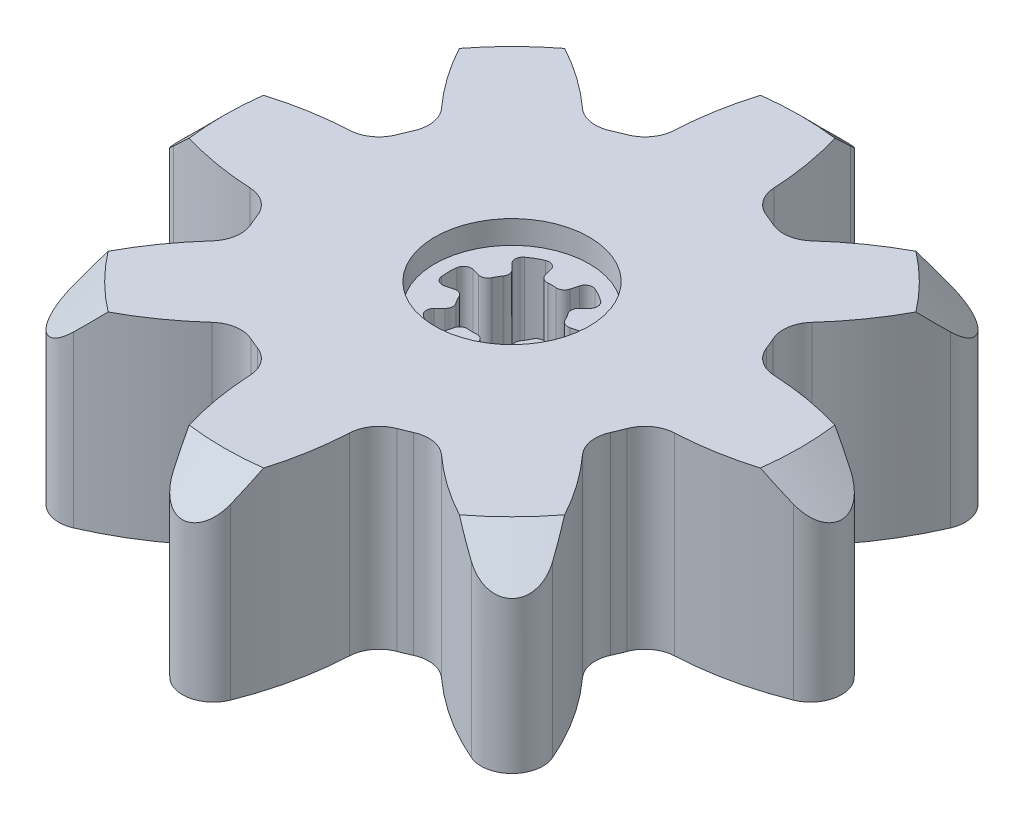
SolidWorks part; units mm, degrees
ref_plane "Front Plane" through (0, 0, 0) normal (0, 0, 1) x (1, 0, 0)
ref_plane "Top Plane" through (0, 0, 0) normal (0, 1, 0) x (1, 0, 0)
ref_plane "Right Plane" through (0, 0, 0) normal (1, 0, 0) x (0, 0, -1)
sketch "Sketch1" plane through (0, 0, 0) normal (0, 1, 0) x (1, 0, 0)
  circle A0 centre (0, 0) radius 23.65
  dimension "D1" = 47.3
extrude "Boss-Extrude1" add sketch "Sketch1" along normal blind 12.5
sketch "Sketch2" plane through (0, 12.5, 0) normal (0, 1, 0) x (1, 0, 0)
  line L0 (11.3385, 6.7423) -> (11.0415, 6.4453)
  line L2 (6.7423, 11.3385) -> (6.4453, 11.0415)
  line L3 (-3.25, 12.785) -> (-3.25, 12.365)
  line L4 (3.25, 12.785) -> (3.25, 12.365)
  line L5 (12.785, -3.25) -> (12.365, -3.25)
  line L6 (12.785, 3.25) -> (12.365, 3.25)
  line L7 (6.7423, -11.3385) -> (6.4453, -11.0415)
  line L8 (11.3385, -6.7423) -> (11.0415, -6.4453)
  line L9 (-3.25, -12.785) -> (-3.25, -12.365)
  line L10 (3.25, -12.785) -> (3.25, -12.365)
  line L11 (-11.3385, -6.7423) -> (-11.0415, -6.4453)
  line L12 (-6.7423, -11.3385) -> (-6.4453, -11.0415)
  line L13 (-12.785, 3.25) -> (-12.365, 3.25)
  line L14 (-12.785, -3.25) -> (-12.365, -3.25)
  line L15 (-6.7423, 11.3385) -> (-6.4453, 11.0415)
  line L16 (-11.3385, 6.7423) -> (-11.0415, 6.4453)
  circle A0 centre (0, 0) radius 12.785
  arc A1 (16.7231, 16.7231) -> (6.7423, 11.3385) centre (20.7333, -2.6525) ccw
  arc A4 (16.7231, 16.7231) -> (11.3385, 6.7423) centre (-2.6525, 20.7333) cw
  arc A5 (23.65, 0) -> (12.785, 3.25) centre (12.785, -16.5363) ccw
  arc A6 (23.65, 0) -> (12.785, -3.25) centre (12.785, 16.5363) cw
  arc A7 (16.7231, -16.7231) -> (11.3385, -6.7423) centre (-2.6525, -20.7333) ccw
  arc A8 (16.7231, -16.7231) -> (6.7423, -11.3385) centre (20.7333, 2.6525) cw
  arc A9 (0, -23.65) -> (3.25, -12.785) centre (-16.5363, -12.785) ccw
  arc A10 (0, -23.65) -> (-3.25, -12.785) centre (16.5363, -12.785) cw
  arc A11 (-16.7231, -16.7231) -> (-6.7423, -11.3385) centre (-20.7333, 2.6525) ccw
  arc A12 (-16.7231, -16.7231) -> (-11.3385, -6.7423) centre (2.6525, -20.7333) cw
  arc A13 (-23.65, 0) -> (-12.785, -3.25) centre (-12.785, 16.5363) ccw
  arc A14 (-23.65, 0) -> (-12.785, 3.25) centre (-12.785, -16.5363) cw
  arc A15 (-16.7231, 16.7231) -> (-11.3385, 6.7423) centre (2.6525, 20.7333) ccw
  arc A16 (-16.7231, 16.7231) -> (-6.7423, 11.3385) centre (-20.7333, -2.6525) cw
  circle A18 centre (0, 0) radius 23.65
  arc A19 (0, 23.65) -> (-3.25, 12.785) centre (16.5363, 12.785) ccw
  arc A20 (0, 23.65) -> (3.25, 12.785) centre (-16.5363, 12.785) cw
  point P9 (0, 12.785)
  point P11 (0, 11.65)
  point P50 (0.2071, 0.5)
  point P65 (0, 0)
  circle M22 centre (0, 0) radius 23.65
  dimension "D1" = 6.5
  dimension "D2" = 47.3
  dimension "D3" = 25.57
chamfer "Chamfer1" distance 5 angle 45 1 edges at (0, 12.5, 23.65)
extrude "Cut-Extrude1" cut sketch "Sketch2" against normal through all contours A0 M22 | A0 M22 | A0 M22 | A0 M22 | A0 M22 | A0 M22 | A0 M22 | A0 M22 region at (17.8273, 12.5, -7.3843) region at (7.3843, 12.5, -17.8273) region at (17.8273, 12.5, 7.3843) region at (-7.3843, 12.5, -17.8273) region at (7.3843, 12.5, 17.8273) region at (-17.8273, 12.5, -7.3843) region at (-7.3843, 12.5, 17.8273) region at (-17.8273, 12.5, 7.3843)
sketch "Sketch3" plane through (0, 0, 0) normal (0, -1, 0) x (1, 0, 0)
  line L1 (0.6729, 2.5114) -> (1.0612, 3.9603)
  line L3 (1.8385, 1.8385) -> (2.8991, 2.8991)
  line L5 (2.5114, 0.6729) -> (3.9603, 1.0612)
  line L7 (2.5114, -0.6729) -> (3.9603, -1.0612)
  line L9 (1.8385, -1.8385) -> (2.8991, -2.8991)
  line L11 (0.6729, -2.5114) -> (1.0612, -3.9603)
  line L13 (-0.6729, -2.5114) -> (-1.0612, -3.9603)
  line L15 (-1.8385, -1.8385) -> (-2.8991, -2.8991)
  line L17 (-2.5114, -0.6729) -> (-3.9603, -1.0612)
  line L19 (-2.5114, 0.6729) -> (-3.9603, 1.0612)
  line L21 (-1.8385, 1.8385) -> (-2.8991, 2.8991)
  line L23 (-0.6729, 2.5114) -> (-1.0612, 3.9603)
  line L31 (9.8199, 4.8449) -> (4.3018, 2.5484)
  line L32 (10.3578, 3.5523) -> (4.8397, 1.2559)
  line L33 (10.3695, -3.5179) -> (4.8438, -1.2398)
  line L34 (3.1234, 9.4126) -> (3.4218, 10.1365)
  line L35 (3.5179, 10.3695) -> (1.2398, 4.8438)
  line L36 (4.4177, 8.879) -> (4.7161, 9.6029)
  line L37 (4.8122, 9.8359) -> (2.5341, 4.3102)
  line L38 (9.8359, -4.8122) -> (4.3102, -2.5341)
  line L39 (4.8449, -9.8199) -> (2.5484, -4.3018)
  line L40 (3.5523, -10.3578) -> (1.2559, -4.8397)
  line L41 (-3.5179, -10.3695) -> (-1.2398, -4.8438)
  line L42 (-4.8122, -9.8359) -> (-2.5341, -4.3102)
  line L43 (-9.8199, -4.8449) -> (-4.3018, -2.5484)
  line L44 (-10.3578, -3.5523) -> (-4.8397, -1.2559)
  line L45 (-10.3695, 3.5179) -> (-4.8438, 1.2398)
  line L46 (-9.8359, 4.8122) -> (-4.3102, 2.5341)
  line L47 (-4.8449, 9.8199) -> (-2.5484, 4.3018)
  line L48 (-3.5523, 10.3578) -> (-1.2559, 4.8397)
  circle A0 centre (0, 0) radius 5
  circle A1 centre (0, 0) radius 4.1
  arc A2 (-1.8385, 1.8385) -> (-2.5114, 0.6729) centre (0, 0) ccw
  arc A3 (0.6729, 2.5114) -> (-0.6729, 2.5114) centre (0, 0) ccw
  arc A4 (2.5114, 0.6729) -> (1.8385, 1.8385) centre (0, 0) ccw
  arc A5 (1.8385, -1.8385) -> (2.5114, -0.6729) centre (0, 0) ccw
  arc A6 (-0.6729, -2.5114) -> (0.6729, -2.5114) centre (0, 0) ccw
  arc A7 (-2.5114, -0.6729) -> (-1.8385, -1.8385) centre (0, 0) ccw
  arc A8 (5.6717, 9.3667) -> (6.8899, 9.5082) centre (6.1897, 10.2221) ccw
  arc A9 (0.1771, 19.653) -> (1.8155, 11.604) centre (-19.7992, 11.3955) cw
  arc A10 (-0.1922, 19.6539) -> (-1.8514, 11.5952) centre (19.5501, 11.3892) ccw
  arc A11 (-14.0333, 13.7614) -> (-9.5082, 6.8899) centre (5.7706, 21.8774) ccw
  arc A12 (-13.7716, 14.022) -> (-6.9215, 9.489) centre (-22.058, -5.9423) cw
  arc A13 (-13.7716, 14.022) -> (-14.0333, 13.7614) centre (-13.8483, 13.8373) ccw
  arc A14 (-9.3667, 5.6717) -> (-10.6418, 2.5798) centre (0, 0) ccw
  arc A15 (0.1771, 19.653) -> (-0.1922, 19.6539) centre (-0.0078, 19.5766) ccw
  arc A16 (14.022, 13.7716) -> (9.489, 6.9215) centre (-5.9423, 22.058) cw
  arc A17 (13.7614, 14.0333) -> (6.8899, 9.5082) centre (21.8774, -5.7706) ccw
  arc A18 (14.022, 13.7716) -> (13.7614, 14.0333) centre (13.8373, 13.8483) ccw
  arc A19 (19.653, -0.1771) -> (11.604, -1.8155) centre (11.3955, 19.7992) cw
  arc A20 (19.6539, 0.1922) -> (11.5952, 1.8514) centre (11.3892, -19.5501) ccw
  arc A21 (19.653, -0.1771) -> (19.6539, 0.1922) centre (19.5766, 0.0078) ccw
  arc A22 (13.7716, -14.022) -> (6.9215, -9.489) centre (22.058, 5.9423) cw
  arc A23 (14.0333, -13.7614) -> (9.5082, -6.8899) centre (-5.7706, -21.8774) ccw
  arc A24 (13.7716, -14.022) -> (14.0333, -13.7614) centre (13.8483, -13.8373) ccw
  arc A25 (-0.1771, -19.653) -> (-1.8155, -11.604) centre (19.7992, -11.3955) cw
  arc A26 (0.1922, -19.6539) -> (1.8514, -11.5952) centre (-19.5501, -11.3892) ccw
  arc A27 (-0.1771, -19.653) -> (0.1922, -19.6539) centre (0.0078, -19.5766) ccw
  arc A28 (-14.022, -13.7716) -> (-9.489, -6.9215) centre (5.9423, -22.058) cw
  arc A29 (-13.7614, -14.0333) -> (-6.8899, -9.5082) centre (-21.8774, 5.7706) ccw
  arc A30 (-14.022, -13.7716) -> (-13.7614, -14.0333) centre (-13.8373, -13.8483) ccw
  arc A31 (-19.653, 0.1771) -> (-11.604, 1.8155) centre (-11.3955, -19.7992) cw
  arc A32 (-19.6539, -0.1922) -> (-11.5952, -1.8514) centre (-11.3892, 19.5501) ccw
  arc A33 (-19.653, 0.1771) -> (-19.6539, -0.1922) centre (-19.5766, -0.0078) ccw
  arc A34 (-2.6127, 10.6337) -> (-5.7006, 9.3491) centre (0, 0) ccw
  arc A35 (5.6717, 9.3667) -> (2.5798, 10.6418) centre (0, 0) ccw
  arc A36 (10.6337, 2.6127) -> (9.3491, 5.7006) centre (0, 0) ccw
  arc A37 (9.3667, -5.6717) -> (10.6418, -2.5798) centre (0, 0) ccw
  arc A38 (2.6127, -10.6337) -> (5.7006, -9.3491) centre (0, 0) ccw
  arc A39 (-5.6717, -9.3667) -> (-2.5798, -10.6418) centre (0, 0) ccw
  arc A40 (-10.6337, -2.6127) -> (-9.3491, -5.7006) centre (0, 0) ccw
  arc A43 (11.5952, 1.8514) -> (10.6337, 2.6127) centre (11.6048, 2.8513) cw
  arc A44 (10.6418, -2.5798) -> (11.604, -1.8155) centre (11.6136, -2.8154) cw
  arc A45 (9.5082, -6.8899) -> (9.3667, -5.6717) centre (10.2221, -6.1897) cw
  arc A46 (5.7006, -9.3491) -> (6.9215, -9.489) centre (6.2213, -10.2029) cw
  arc A47 (1.8514, -11.5952) -> (2.6127, -10.6337) centre (2.8513, -11.6048) cw
  arc A48 (-2.5798, -10.6418) -> (-1.8155, -11.604) centre (-2.8154, -11.6136) cw
  arc A49 (-6.8899, -9.5082) -> (-5.6717, -9.3667) centre (-6.1897, -10.2221) cw
  arc A50 (-9.3491, -5.7006) -> (-9.489, -6.9215) centre (-10.2029, -6.2213) cw
  arc A51 (-11.5952, -1.8514) -> (-10.6337, -2.6127) centre (-11.6048, -2.8513) cw
  arc A52 (-10.6418, 2.5798) -> (-11.604, 1.8155) centre (-11.6136, 2.8154) cw
  arc A53 (-9.5082, 6.8899) -> (-9.3667, 5.6717) centre (-10.2221, 6.1897) cw
  arc A54 (-5.7006, 9.3491) -> (-6.9215, 9.489) centre (-6.2213, 10.2029) cw
  arc A55 (-1.8514, 11.5952) -> (-2.6127, 10.6337) centre (-2.8513, 11.6048) cw
  arc A56 (2.5798, 10.6418) -> (1.8155, 11.604) centre (2.8154, 11.6136) cw
  arc A57 (9.489, 6.9215) -> (9.3491, 5.7006) centre (10.2029, 6.2213) ccw
  point P31 (0, 0)
  point P110 (0, 0)
  point P113 (3.7705, 9.1458)
  point P148 (0, 0)
  point P196 (0, 0)
  dimension "D1" = 10
  dimension "D2" = 8.2
  dimension "D3" = 5.2
  dimension "D5" = 0.2
  dimension "D6" = 21.9
  dimension "D10" = 1
  dimension "D4" = 1
  dimension "D8" = 1.4
  dimension "D7" = 8
  dimension "D9" = 8
extrude "Cut-Extrude3" cut sketch "Sketch3" against normal blind 9 contours A34 A54 A12 A13 A11 A53 A14 L46 A0 L47 | A35 A56 A9 A15 A10 A55 A34 L48 A0 L35 L34 | A57 A16 A18 A17 A8 A35 L37 L36 A0 L31 A36 | A37 A44 A19 A21 A20 A43 A36 L32 A0 L33 | A38 A46 A22 A24 A23 A45 A37 L38 A0 L39 | A39 A48 A25 A27 A26 A47 A38 L40 A0 L41 | A40 A50 A28 A30 A29 A49 A39 L42 A0 L43 | A14 A52 A31 A33 A32 A51 A40 L44 A0 L45 | L17 A7 L15 A1 L13 A6 L11 L9 A5 L7 L5 A4 L3 L1 A3 L23 L21 A2 L19 region at (0, 0, 0) region at (7.7806, 0, 7.8015) region at (11.0182, 0, 0.0148) region at (-0.0148, 0, 11.0182) region at (7.8015, 0, -7.7806) region at (-7.8015, 0, 7.7806) region at (0.0148, 0, -11.0182) region at (-11.0182, 0, -0.0148) region at (-7.7806, 0, -7.8015)
extrude "Cut-Extrude4" cut sketch "Sketch3<4>" against normal through all contours L17 A7 L15 A1 L13 A6 L11 L9 A5 L7 L5 A4 L3 L1 A3 L23 L21 A2 L19 region at (0, 0, 0)
sketch "Sketch3<4>" plane through (0, 0, 0) normal (0, -1, 0) x (1, 0, 0) same geometry as "Sketch3"
extrude "Boss-Extrude2" add sketch "Sketch3<5>" along normal blind 5 contours A0 A1 | A3 L1 A1 L23 | A2 L21 A1 L19 | A7 L17 A1 L15 | A6 L13 A1 L11 | A5 L9 A1 L7 | A4 L5 A1 L3 region at (0, 0, 3.3672) region at (2.9161, 0, 1.6836) region at (-2.9161, 0, 1.6836) region at (2.9161, 0, -1.6836) region at (-2.9161, 0, -1.6836) region at (0, 0, -3.3672) region at (4.4856, 0, 1.8668)
sketch "Sketch3<5>" plane through (0, 0, 0) normal (0, -1, 0) x (1, 0, 0) same geometry as "Sketch3"
extrude "Cut-Extrude5" cut sketch "Sketch3<7>" against normal through all from offset 11 contours A0 A1 | A4 L5 A1 L3 | A3 L1 A1 L23 | A5 L9 A1 L7 | A2 L21 A1 L19 | A7 L17 A1 L15 | A6 L13 A1 L11 region at (0, 0, 3.3672) region at (2.9161, 0, 1.6836) region at (-2.9161, 0, 1.6836) region at (2.9161, 0, -1.6836) region at (-2.9161, 0, -1.6836) region at (0, 0, -3.3672) region at (4.4856, 0, 1.8668) offset against normal yes
sketch "Sketch3<7>" plane through (0, 0, 0) normal (0, -1, 0) x (1, 0, 0) same geometry as "Sketch3"
fillet "Fillet2" radius 0.5 24 edges at (-2.5114, 3, -0.6729) (2.5114, 3, 0.6729) (0.6729, 3, 2.5114) (-0.6729, 3, -2.5114) (-1.8385, 3, 1.8385) (1.8385, 3, -1.8385) (-2.8991, 3, 2.8991) (2.8991, 3, -2.8991) (-1.0612, 3, 3.9603) (1.0612, 3, -3.9603) (-3.9603, 3, -1.0612) (3.9603, 3, 1.0612) (2.8991, 3, 2.8991) (-2.8991, 3, -2.8991) (1.0612, 3, 3.9603) (-1.0612, 3, -3.9603) (-0.6729, 3, 2.5114) (0.6729, 3, -2.5114) (-3.9603, 3, 1.0612) (3.9603, 3, -1.0612) (1.8385, 3, 1.8385) (-1.8385, 3, -1.8385) (-2.5114, 3, 0.6729) (2.5114, 3, -0.6729)
sketch "Sketch5" plane through (0, 12.5, 0) normal (0, 1, 0) x (1, 0, 0)
  line L0 (0.0035, 21.4851) -> (0.0035, 19.9851)
  arc A0 (0.9112, 20.9105) -> (-0.9011, 20.9057) centre (0.0061, 20.4851) ccw construction
  circle A1 centre (0.0035, 19.9851) radius 1
  dimension "D2" = 2
  dimension "D1" = 1.5
extrude "Cut-Extrude6" cut sketch "Sketch5" against normal through all and the other way through all contours A1 region at (-0.6836, 12.5, -19.298)
fillet "Fillet3" radius 2 23 edges at (23.65, 3.75, 0) (16.7231, 3.75, 16.7231) (12.365, 6.25, 3.25) (11.0415, 6.25, 6.4453) (16.7231, 3.75, -16.7231) (6.4453, 6.25, -11.0415) (11.0415, 6.25, -6.4453) (12.365, 6.25, -3.25) (3.25, 6.25, -12.365) (-6.4453, 6.25, -11.0415) (-3.25, 6.25, -12.365) (-16.7231, 3.75, -16.7231) (-11.0415, 6.25, -6.4453) (-12.365, 6.25, -3.25) (-23.65, 3.75, 0) (-11.0415, 6.25, 6.4453) (-12.365, 6.25, 3.25) (-16.7231, 3.75, 16.7231) (-6.4453, 6.25, 11.0415) (-3.25, 6.25, 12.365) (6.4453, 6.25, 11.0415) (3.25, 6.25, 12.365) (0, 3.75, 23.65)
fillet "Fillet4" radius 2 1 edges at (0, 3.75, -23.65)
